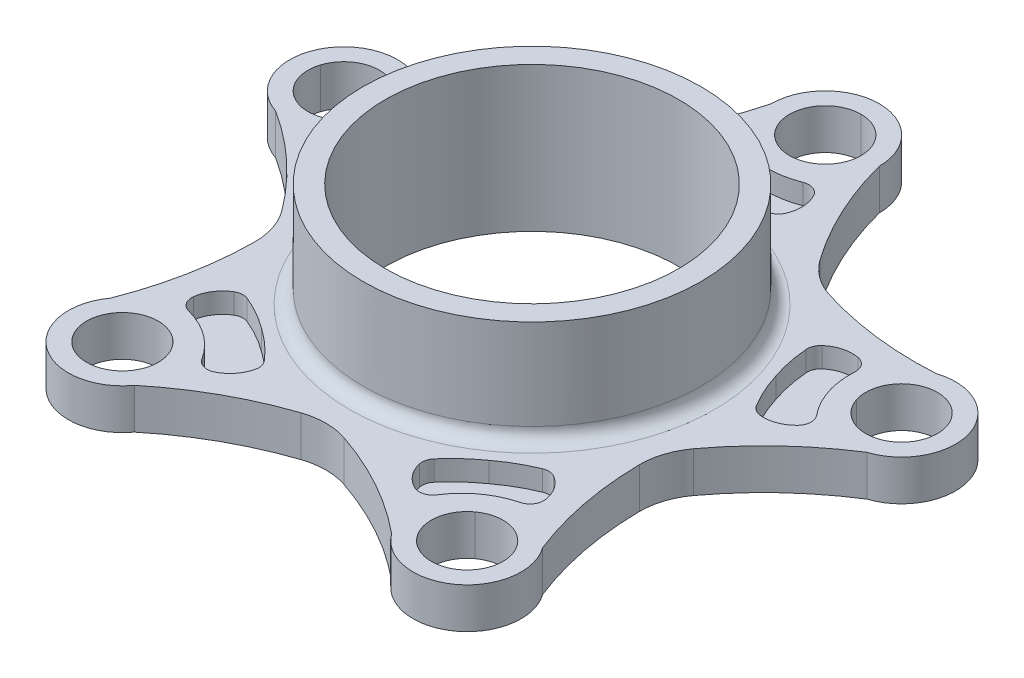
SolidWorks part; units mm, degrees
ref_plane "Front Plane" through (0, 0, 0) normal (0, 0, 1) x (1, 0, 0)
ref_plane "Top Plane" through (0, 0, 0) normal (0, 1, 0) x (1, 0, 0)
ref_plane "Right Plane" through (0, 0, 0) normal (1, 0, 0) x (0, 0, -1)
sketch "Sketch1" plane through (0, 0, 0) normal (0, 1, 0) x (1, 0, 0)
  circle A0 centre (0, 0) radius 31.75
  dimension "D1" = 63.5
extrude "CenterCircleExtrude" add sketch "Sketch1" along normal blind 19.558 contours A0
sketch "Sketch2" plane through (0, 0, 0) normal (0, -1, 0) x (1, 0, 0)
  circle A0 centre (0, 0) radius 80.01
  dimension "D1" = 160.02
extrude "BaseExpand" add sketch "Sketch2" along normal blind 7.62
sketch "Sketch3" plane through (0, 19.558, 0) normal (0, 1, 0) x (1, 0, 0)
  circle A0 centre (0, 0) radius 27.559
  dimension "D1" = 55.118
extrude "CenterCut" cut sketch "Sketch3" against normal blind 27.178 contours A0
sketch "Sketch4" plane through (0, 0, 0) normal (0, 1, 0) x (1, 0, 0)
  line L0 (-52.4203, 17.0324) -> (0, 55.118) construction
  line L1 (-26.2102, 36.0752) -> (-18.6622, 25.6863) construction
  circle A0 centre (0, 55.118) radius 6.731
  circle A1 centre (52.4203, 17.0324) radius 6.731
  circle A2 centre (32.3975, -44.5914) radius 6.731
  circle A3 centre (-32.3975, -44.5914) radius 6.731
  circle A4 centre (-52.4203, 17.0324) radius 6.731
  circle A5 centre (0, 0) radius 31.75 construction
  point P14 (0, 0)
  dimension "D1" = 13.462
  dimension "D2" = 55.118
  dimension "D3" = 5
extrude "OuterCircleCut" cut sketch "Sketch4" against normal blind 7.62
sketch "Sketch8" plane through (0, 0, 0) normal (0, 1, 0) x (1, 0, 0)
  line L0 (-52.4203, 17.0324) -> (0, 55.118) construction
  line L1 (-26.2102, 36.0752) -> (-18.6622, 25.6863) construction
  line L2 (26.2102, 36.0752) -> (18.6622, 25.6863) construction
  line L3 (42.4089, -13.7795) -> (30.196, -9.8113) construction
  line L4 (0, -44.5914) -> (0, -31.75) construction
  line L5 (-42.4089, -13.7795) -> (-30.196, -9.8113) construction
  line L6 (0, 0) -> (-22.4362, 30.8807) construction
  line L7 (0, 0) -> (22.4362, 30.8807) construction
  line L8 (0, 0) -> (10.16, 55.118) construction
  line L9 (10.16, 55.118) -> (-10.16, 55.118) construction
  circle A0 centre (-52.4203, 17.0324) radius 10.16
  circle A1 centre (0, 55.118) radius 10.16
  circle A2 centre (52.4203, 17.0324) radius 10.16
  circle A3 centre (32.3975, -44.5914) radius 10.16
  circle A4 centre (-32.3975, -44.5914) radius 10.16
  circle A5 centre (0, 0) radius 31.75 construction
  arc A6 (10.16, 55.118) -> (22.4362, 30.8807) centre (71.6347, 71.0274) ccw
  arc A7 (-22.4362, 30.8807) -> (-10.16, 55.118) centre (-71.6347, 71.0274) ccw
  arc A8 (22.4362, 30.8807) -> (49.2807, 26.6951) centre (45.4147, 90.0773) ccw
  arc A9 (55.5599, 7.3697) -> (36.3025, -11.7954) centre (89.6874, -46.18) ccw
  arc A10 (36.3025, -11.7954) -> (40.6172, -38.6195) centre (99.7026, -15.3565) ccw
  arc A11 (24.1779, -50.5633) -> (0, -38.1707) centre (-16.2049, -99.5682) ccw
  arc A12 (0, -38.1707) -> (-24.1779, -50.5633) centre (16.2049, -99.5682) ccw
  arc A13 (-40.6172, -38.6195) -> (-36.3025, -11.7954) centre (-99.7026, -15.3565) ccw
  arc A14 (-36.3025, -11.7954) -> (-55.5599, 7.3697) centre (-89.6874, -46.18) ccw
  arc A15 (-49.2807, 26.6951) -> (-22.4362, 30.8807) centre (-45.4147, 90.0773) ccw
  point P14 (0, 0)
  point P27 (0, 0)
  point P72 (0, 0)
  circle M12 centre (0, 0) radius 80.01
  dimension "D1" = 5
  dimension "D3" = 5
  dimension "D5" = 5
  dimension "D4" = 72
  dimension "D2" = 5
extrude "StarfishCut" cut sketch "Sketch8" against normal blind 7.62 contours A0 A15 A7 A1 A6 A8 A2 A9 A10 A3 A11 A12 A4 A13 A14 M12 region at (-77.747, 0, 0)
fillet "Fillet8" radius 2.54 1 edges at (0, 0, 31.75)
fillet "Fillet10" radius 12.7 5 edges at (-22.4362, -3.81, -30.8807) (-36.3025, -3.81, 11.7954) (0, -3.81, 38.1707) (36.3025, -3.81, 11.7954) (22.4362, -3.81, -30.8807)
sketch "Sketch14" plane through (0, 0, 0) normal (0, 1, 0) x (1, 0, 0)
  line L4 (0, -14.9479) -> (0, 14.9479) construction
  arc A0 (38.2121, 3.6164) -> (34.5928, 11.2399) centre (62.2856, 19.7161) cw
  arc A1 (33.0399, 19.5348) -> (34.5928, 11.2399) centre (61.9789, 20.6599) ccw
  arc A2 (41.5686, 21.0847) -> (33.0399, 19.5348) centre (38.134, 15.7437) ccw
  arc A25 (7.2074, 46.0496) -> (-7.2074, 46.0496) centre (0, 59.4776) cw
  arc A26 (-7.2074, 46.0496) -> (-8.3688, 37.4594) centre (-3.1891, 41.1327) ccw
  arc A27 (-8.3688, 37.4594) -> (0, 36.3731) centre (-0.4961, 65.3297) ccw
  arc A45 (8.3688, 37.4594) -> (0, 36.3731) centre (0.4961, 65.3297) cw
  arc A46 (7.2074, 46.0496) -> (8.3688, 37.4594) centre (3.1891, 41.1327) cw
  arc A47 (46.023, 7.3755) -> (41.5686, 21.0847) centre (56.5665, 18.3796) cw
  arc A48 (46.023, 7.3755) -> (38.2121, 3.6164) centre (40.105, 9.6777) cw
  arc A49 (15.2476, -35.2243) -> (21.3796, -29.4264) centre (37.9984, -53.1445) cw
  arc A50 (28.7886, -25.3862) -> (21.3796, -29.4264) centre (38.8012, -52.5612) ccw
  arc A51 (32.8982, -33.0185) -> (28.7886, -25.3862) centre (26.7572, -31.4026) ccw
  arc A52 (21.2364, -41.4913) -> (32.8982, -33.0185) centre (34.96, -48.1184) cw
  arc A53 (21.2364, -41.4913) -> (15.2476, -35.2243) centre (21.5972, -35.1516) cw
  arc A54 (-28.7886, -25.3862) -> (-21.3796, -29.4264) centre (-38.8012, -52.5612) cw
  arc A55 (-15.2476, -35.2243) -> (-21.3796, -29.4264) centre (-37.9984, -53.1445) ccw
  arc A56 (-21.2364, -41.4913) -> (-15.2476, -35.2243) centre (-21.5972, -35.1516) ccw
  arc A57 (-32.8982, -33.0185) -> (-21.2364, -41.4913) centre (-34.96, -48.1184) cw
  arc A58 (-32.8982, -33.0185) -> (-28.7886, -25.3862) centre (-26.7572, -31.4026) cw
  arc A59 (-33.0399, 19.5348) -> (-34.5928, 11.2399) centre (-61.9789, 20.6599) cw
  arc A60 (-38.2121, 3.6164) -> (-34.5928, 11.2399) centre (-62.2856, 19.7161) ccw
  arc A61 (-46.023, 7.3755) -> (-38.2121, 3.6164) centre (-40.105, 9.6777) ccw
  arc A62 (-41.5686, 21.0847) -> (-46.023, 7.3755) centre (-56.5665, 18.3796) cw
  arc A63 (-41.5686, 21.0847) -> (-33.0399, 19.5348) centre (-38.134, 15.7437) cw
  point P34 (0, 0)
  point P51 (0, 0)
  point P61 (0, 0)
  point P97 (0, 0)
  dimension "D1" = 6.35
  dimension "D2" = 15.24
  dimension "D4" = 5
  dimension "D3" = 28.9609
extrude "Batman Cut" cut sketch "Sketch14" against normal blind 3.81
fillet "Fillet11" radius 2.54 20 edges at (21.2364, -1.905, 41.4913) (32.8982, -1.905, 33.0185) (28.7886, -1.905, 25.3862) (15.2476, -1.905, 35.2243) (-21.2364, -1.905, 41.4913) (-32.8982, -1.905, 33.0185) (-15.2476, -1.905, 35.2243) (-28.7886, -1.905, 25.3862) (-38.2121, -1.905, -3.6164) (-46.023, -1.905, -7.3755) (-33.0399, -1.905, -19.5348) (-41.5686, -1.905, -21.0847) (38.2121, -1.905, -3.6164) (33.0399, -1.905, -19.5348) (46.023, -1.905, -7.3755) (41.5686, -1.905, -21.0847) (-8.3688, -1.905, -37.4594) (8.3688, -1.905, -37.4594) (-7.2074, -1.905, -46.0496) (7.2074, -1.905, -46.0496)
ref_plane "Plane1" through (0, 0, 0) normal (-1, 0, 0) x (0, 0, 1)
ref_plane "Plane2" through (0, 0, 0) normal (-0.309, 0, 0.9511) x (0.9511, 0, 0.309)
ref_plane "Plane3" through (0, 0, 0) normal (0.809, 0, -0.5878) x (-0.5878, 0, -0.809)
ref_plane "Plane4" through (0, 0, 0) normal (0.809, 0, 0.5878) x (0.5878, 0, -0.809)
ref_plane "Plane5" through (0, 0, 0) normal (-0.309, 0, -0.9511) x (-0.9511, 0, 0.309)
split line "Split Line1"
split line "Split Line2"
split line "Split Line3"
split line "Split Line4"
split line "Split Line5"
ref_plane "Plane6" through (52.4203, 0, -17.0324) normal (0.9511, 0, -0.309) x (-0.309, 0, -0.9511)
ref_plane "Plane7" through (32.3975, 0, 44.5914) normal (-0.5878, 0, -0.809) x (-0.809, 0, 0.5878)
ref_plane "Plane8" through (-32.3975, 0, 44.5914) normal (0.5878, 0, -0.809) x (-0.809, 0, -0.5878)
ref_plane "Plane9" through (-52.4203, 0, -17.0324) normal (0.9511, 0, 0.309) x (0.309, 0, -0.9511)
ref_plane "Plane10" through (0, 0, -55.118) normal (0, 0, 1) x (1, 0, 0)
ref_axis "Axis1" through (0, -7.62, 0) along (0, 1, 0)
